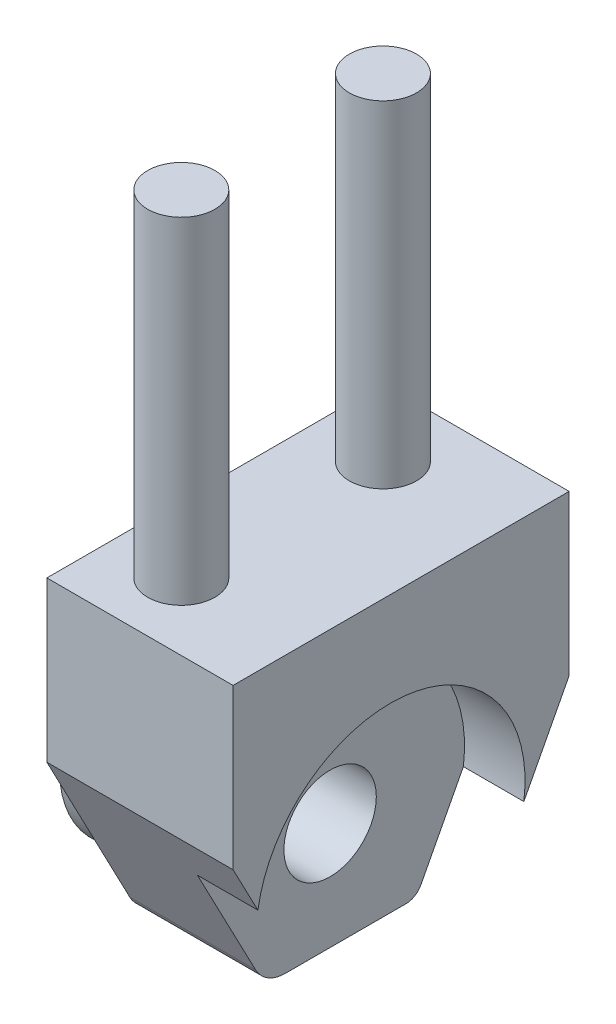
SolidWorks part; units mm, degrees
material "3.0205 (EN-AW 1200)"
ref_plane "Plan de face" through (0, 0, 0) normal (0, 0, 1) x (1, 0, 0)
ref_plane "Plan de dessus" through (0, 0, 0) normal (0, 1, 0) x (1, 0, 0)
ref_plane "Plan de droite" through (0, 0, 0) normal (1, 0, 0) x (0, 0, -1)
sketch "Esquisse1" plane through (0, 0, 0) normal (0, 1, 0) x (1, 0, 0)
  line L1 (15.8141, 19.6321) -> (37.9741, 19.6321)
  line L2 (15.8141, 19.6321) -> (15.8141, -20.3679)
  line L3 (15.8141, -20.3679) -> (37.9741, -20.3679)
  line L4 (37.9741, 19.6321) -> (37.9741, -20.3679)
  dimension "D1" = 40
  dimension "D2" = 22.16
extrude "Boss.-Extru.1" add sketch "Esquisse1" along normal blind 40
chamfer "Chanfrein1" distance 11 distance2 21 1 edges at (26.8941, 0, 20.3679) first distance on face at (26.8941, 0, 0.3679)
chamfer "Chanfrein2" distance 11 distance2 21 1 edges at (26.8941, 0, -19.6321) first distance on face at (26.8941, 0, -5.1321)
fillet "Congé1" radius 4 1 edges at (26.8941, 0, 9.3679)
sketch "Esquisse2" plane through (0, 40, 0) normal (0, 1, 0) x (1, 0, 0)
  line L1 (15.8141, 19.6321) -> (15.8141, -20.3679) construction
  line L2 (15.8141, -20.3679) -> (37.9741, -20.3679) construction
  line L4 (37.9741, 19.6321) -> (15.8141, 19.6321) construction
  circle A0 centre (23.8141, -12.3679) radius 4
  circle A1 centre (23.8141, 11.6321) radius 4
  dimension "D1" = 8
  dimension "D4" = 8
  dimension "D2" = 8
  dimension "D3" = 8
  dimension "D5" = 8
  dimension "D6" = 8
extrude "Boss.-Extru.2" add sketch "Esquisse2" along normal blind 40 contours A1
extrude "Boss.-Extru.3" add sketch "Esquisse2<3>" along normal blind 40
sketch "Esquisse2<3>" plane through (0, 40, 0) normal (0, 1, 0) x (1, 0, 0) same geometry as "Esquisse2"
sketch "Esquisse3" plane through (15.8141, 0, 0) normal (-1, 0, 0) x (0, 0, 1)
  line L0 (-8.6321, 0) -> (6.9476, 0) construction
  line L2 (-19.6321, 40) -> (-19.6321, 21) construction
  circle A0 centre (0.3679, 13.5) radius 12.5
  dimension "D1" = 25
  dimension "D2" = 13.5
  dimension "D3" = 20
extrude "Boss.-Extru.4" add sketch "Esquisse3" along normal blind 6
sketch "Esquisse4" plane through (37.9741, 0, 0) normal (1, 0, 0) x (0, 0, -1)
  line L0 (-20.3679, 40) -> (19.6321, 40) construction
  circle A0 centre (-1.6179, 12.8) radius 16
  dimension "D1" = 32
  dimension "D2" = 27.2
  dimension "D3" = 18.75
extrude "Enlèv. mat.-Extru.1" cut sketch "Esquisse4" against normal blind 7.2
sketch "Esquisse6" plane through (30.7741, 0, 0) normal (1, 0, 0) x (0, 0, -1)
  line L1 (0.8273, 4.7453) -> (12.9159, 4.7453)
  line L2 (0.8273, 4.7453) -> (0.8273, -2.9048)
  line L3 (0.8273, -2.9048) -> (12.9159, -2.9048)
  line L4 (12.9159, 4.7453) -> (12.9159, -2.9048)
extrude "Enlèv. mat.-Extru.2" cut sketch "Esquisse6" along normal through all
fillet "Congé2" radius 2 1 edges at (23.2941, 0, -8.6321)
sketch "Esquisse8" plane through (37.9741, 0, -37.9741) normal (-1, 0, 0) x (0, 0, 1)
  line L1 (58.342, 40) -> (18.342, 40) construction
  circle A0 centre (39.592, 12.8) radius 5.5
  dimension "D1" = 11
  dimension "D2" = 27.2
  dimension "D3" = 18.75
extrude "Enlèv. mat.-Extru.5" cut sketch "Esquisse8" along normal blind 15
